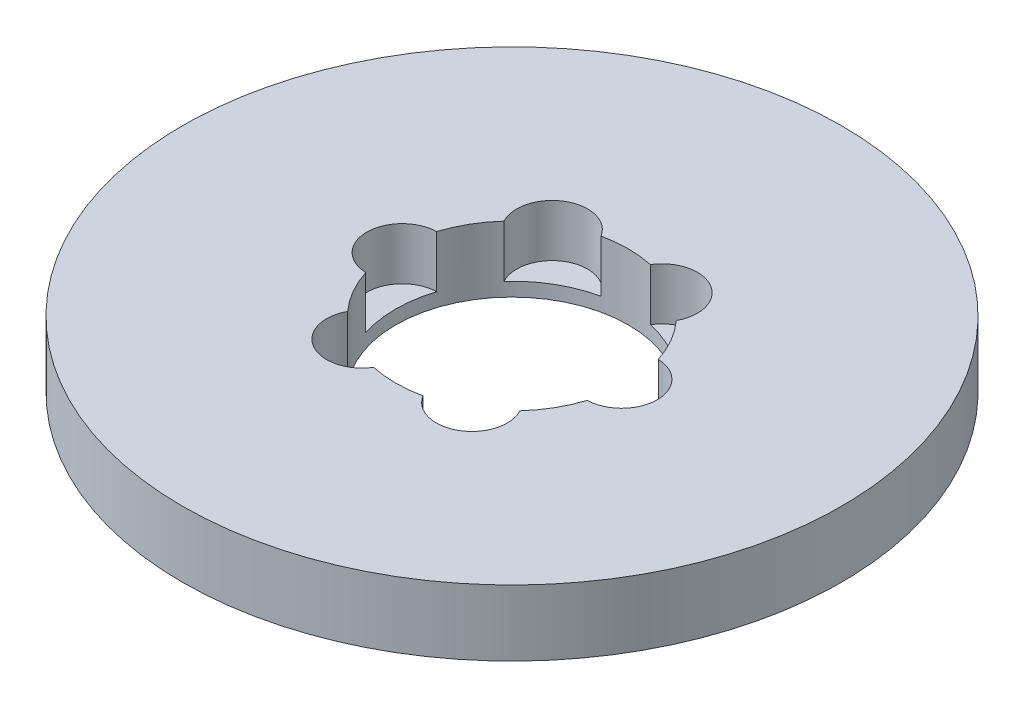
SolidWorks part; units mm, degrees
ref_plane "Front Plane" through (0, 0, 0) normal (0, 0, 1) x (1, 0, 0)
ref_plane "Top Plane" through (0, 0, 0) normal (0, 1, 0) x (1, 0, 0)
ref_plane "Right Plane" through (0, 0, 0) normal (1, 0, 0) x (0, 0, -1)
sketch "Sketch1" plane through (0, 0, 0) normal (0, 1, 0) x (1, 0, 0)
  circle A0 centre (0, 0) radius 85
  dimension "FLANGE_OD" = 170
extrude "Boss-Extrude1" add sketch "Sketch1" along normal blind 17
sketch "Sketch2" plane through (0, 0, 0) normal (0, 1, 0) x (1, 0, 0)
  circle A0 centre (0, 0) radius 30
  dimension "BORE_D" = 60
extrude "Cut-Extrude1" cut sketch "Sketch2" along normal through all
sketch "Sketch3" plane through (0, 17, 0) normal (0, 1, 0) x (1, 0, 0)
  circle A0 centre (0, 0) radius 28.3054 construction
  circle A1 centre (-28.3054, 0) radius 9.1574
  dimension "BOLT_D" = 18.3148
  dimension "BOLT_PCD" = 56.6107
extrude "Cut-Extrude2" cut sketch "Sketch3" against normal blind 13.4413
pattern_circular "CirPattern1" count 6 over 360 about axis through (0, 0, 0) along (0, 1, 0) of "Cut-Extrude2"
